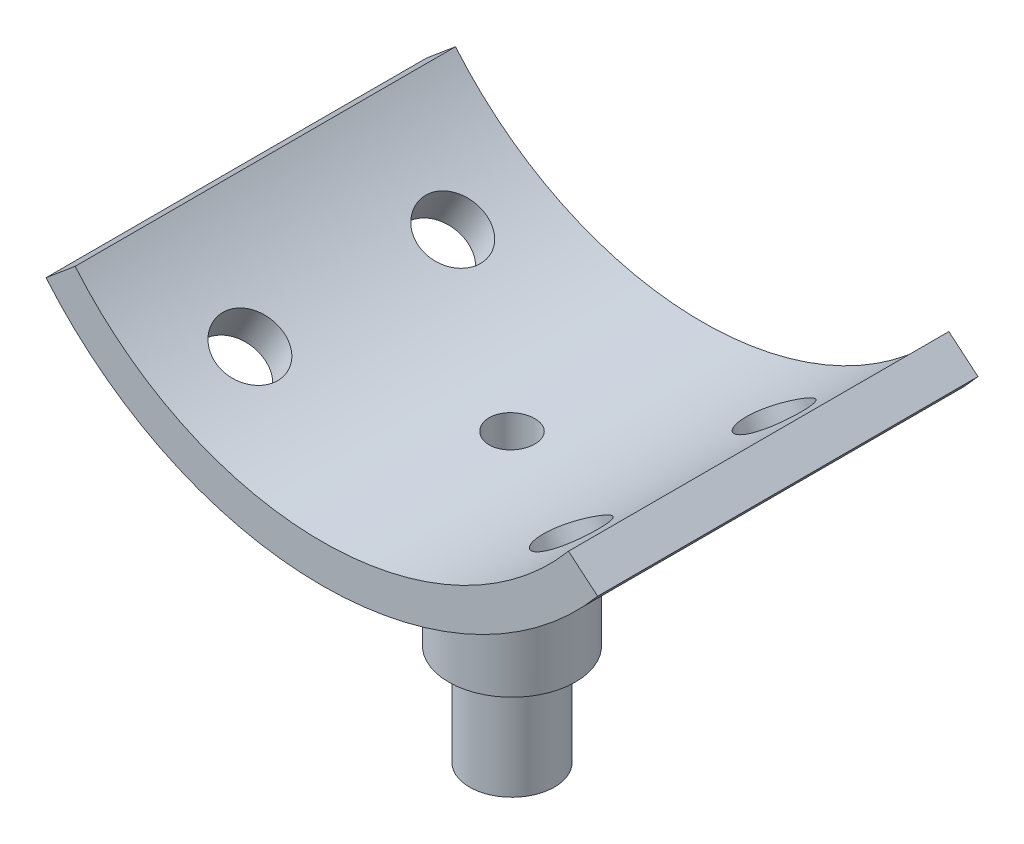
SolidWorks part; units mm, degrees
ref_plane "Front Plane" through (0, 0, 0) normal (0, 0, 1) x (1, 0, 0)
ref_plane "Top Plane" through (0, 0, 0) normal (0, 1, 0) x (1, 0, 0)
ref_plane "Right Plane" through (0, 0, 0) normal (1, 0, 0) x (0, 0, -1)
sketch "Sketch1" plane through (0, 0, 0) normal (0, 0, 1) x (1, 0, 0)
  line L0 (0, 31.2519) -> (0, -31.2519) construction
  line L1 (0, 0) -> (-21.7557, -18.2552) construction
  line L2 (0, 0) -> (21.7557, -18.2552) construction
  line L3 (21.7557, -18.2552) -> (19.4575, -16.3268)
  line L4 (-21.7557, -18.2552) -> (-19.4575, -16.3268)
  arc A0 (-19.4575, -16.3268) -> (19.4575, -16.3268) centre (0, 0) ccw
  arc A1 (-21.7557, -18.2552) -> (21.7557, -18.2552) centre (0, 0) ccw
  circle A2 centre (0, 0) radius 28.4 construction
  circle A3 centre (0, 0) radius 25.4 construction
  point P8 (0, 0)
  dimension "D1" = 50.8
  dimension "D3" = 50
  dimension "D2" = 3
extrude "Boss-Extrude1" add sketch "Sketch1" along normal mid plane 30
ref_plane "Plane1" through (0, -40, 0) normal (0, 1, 0) x (1, 0, 0)
sketch "Sketch2" plane through (0, -40, 0) normal (0, 1, 0) x (1, 0, 0)
  circle A0 centre (0, 0) radius 5
  dimension "D1" = 10
extrude "Boss-Extrude2" add sketch "Sketch2" along normal up to surface (11.6 mm away) up to face at (0, -23.3276, 0)
sketch "Sketch5" plane through (0, 0, 0) normal (0, 0, 1) x (1, 0, 0)
  line L0 (0, 0) -> (14.2, -24.5951) construction
  line L1 (0, 14.0723) -> (0, -38.9472) construction
  line L2 (0, 0) -> (-14.2, -24.5951) construction
  arc A0 (-21.7557, -18.2552) -> (21.7557, -18.2552) centre (0, 0) ccw construction
  dimension "D1" = 30
ref_plane "Plane3" through (14.2, -24.5951, 0) normal (0.5, -0.866, 0) x (-0.866, -0.5, 0)
sketch "Sketch13" plane through (14.2, -24.5951, 0) normal (0.5, -0.866, 0) x (-0.866, -0.5, 0)
  line L0 (-17.4465, 0) -> (25.4678, 0) construction
  circle A1 centre (0, 8) radius 2.5
  circle A2 centre (0, -8) radius 2.5
  dimension "D1" = 5
  dimension "D2" = 8
extrude "Cut-Extrude2" cut sketch "Sketch13" against normal through all
mirror "Mirror1" about plane through (0, 0, 0) normal (1, 0, 0) of "Cut-Extrude2"
sketch "Sketch14" plane through (0, -40, 0) normal (0, -1, 0) x (1, 0, 0)
  circle A0 centre (0, 0) radius 3.35
  dimension "D1" = 6.7
extrude "Boss-Extrude4" add sketch "Sketch14" along normal blind 8
sketch "Sketch4" plane through (0, -40, 0) normal (0, -1, 0) x (1, 0, 0)
  line L0 (-6.6, 0) -> (6.6, 0) construction
  line L5 (-6.6, 0.8) -> (-4.9356, 0.8)
  line L6 (-6.6, 0.8) -> (-6.6, -0.8)
  line L7 (-6.6, -0.8) -> (-4.9356, -0.8)
  line L8 (6.6, 0.8) -> (6.6, -0.8)
  line L9 (0, 12.2903) -> (0, -12.2903) construction
  line L10 (4.9356, 0.8) -> (6.6, 0.8)
  line L11 (4.9356, -0.8) -> (6.6, -0.8)
  circle A0 centre (0, 0) radius 5 construction
  arc A1 (-4.9356, 0.8) -> (-4.9356, -0.8) centre (0, 0) ccw
  arc A2 (4.9356, -0.8) -> (4.9356, 0.8) centre (0, 0) ccw
  point P10 (0, 0)
  point P11 (0, 0)
  point P12 (6.6, 0)
  point P20 (5, 0)
  dimension "D1" = 1.6
  dimension "D2" = 1.6
sketch "Sketch15" plane through (0, -48, 0) normal (0, -1, 0) x (1, 0, 0)
  circle A0 centre (0, 0) radius 1.8
  dimension "D1" = 3.6
extrude "Cut-Extrude3" cut sketch "Sketch15" against normal through all
